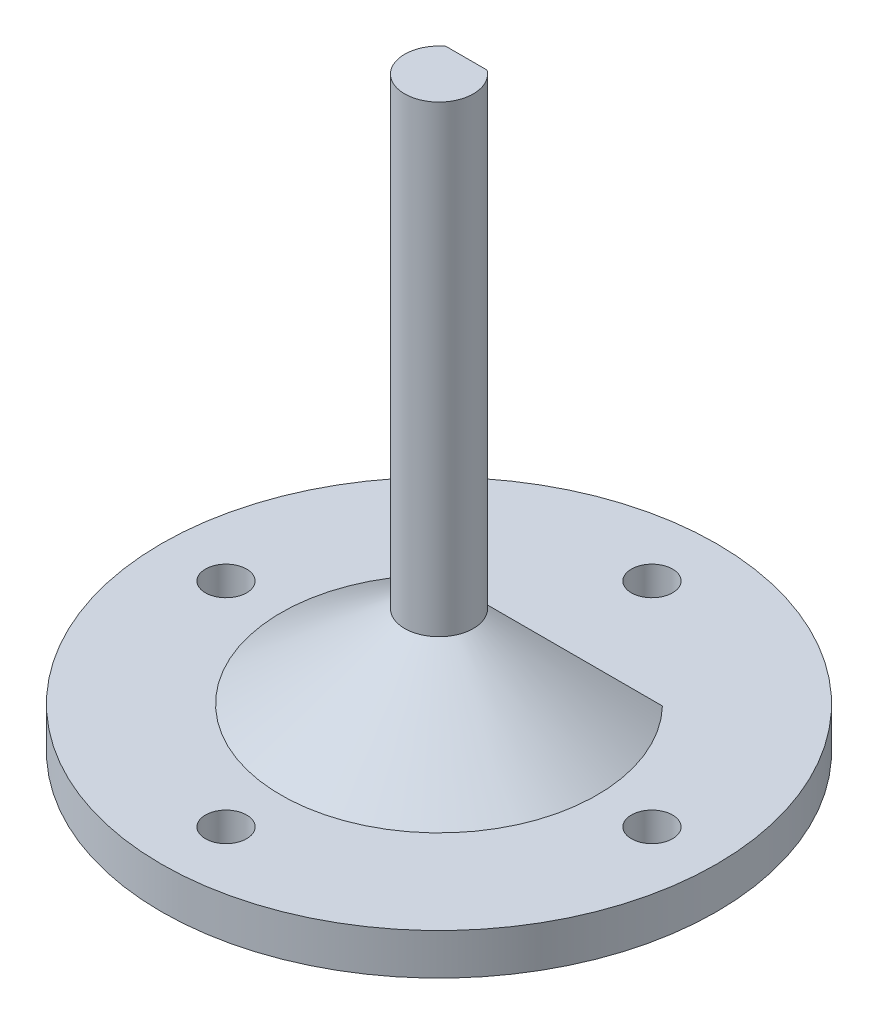
SolidWorks part; units mm, degrees
ref_plane "Front Plane" through (0, 0, 0) normal (0, 0, 1) x (1, 0, 0)
ref_plane "Top Plane" through (0, 0, 0) normal (0, 1, 0) x (1, 0, 0)
ref_plane "Right Plane" through (0, 0, 0) normal (1, 0, 0) x (0, 0, -1)
sketch "Sketch2" plane through (0, 0, 0) normal (0, 1, 0) x (1, 0, 0)
  line L0 (-1.5, 2) -> (1.5, 2)
  circle A0 centre (0, 0) radius 15.5 construction
  circle A1 centre (0, 15.5) radius 1.5
  circle A2 centre (-15.5, 0) radius 1.5
  circle A3 centre (0, -15.5) radius 1.5
  circle A4 centre (15.5, 0) radius 1.5
  circle A5 centre (0, 0) radius 2.5
  circle A6 centre (0, 0) radius 20.2034
  point P15 (0, 0)
  point P16 (0, 0)
  dimension "D2" = 3
  dimension "D3" = 5
  dimension "D1" = 15.5
  dimension "D4" = 2
extrude "Boss-Extrude1" add sketch "Sketch2" against normal blind 3 contours A6 A1 A2 A3 A4 A5 | L0 A5 | L0 A5 region at (0, 0, -2.2018) region at (0, 0, 0.1209) region at (-19.632, 0, 0)
extrude "Boss-Extrude2" add sketch "Sketch2<3>" along normal blind 39.7 contours L0 A5 region at (0, 0, 0.1209)
sketch "Sketch2<3>" plane through (0, 0, 0) normal (0, 1, 0) x (1, 0, 0) same geometry as "Sketch2"
chamfer "Chamfer1" distance 9 distance2 6 1 edges at (0, 0, 2.5) first distance on face at (0, 0, 20.2034)
chamfer "Chamfer2" distance 6 angle 45 1 edges at (0, 0, -2)
